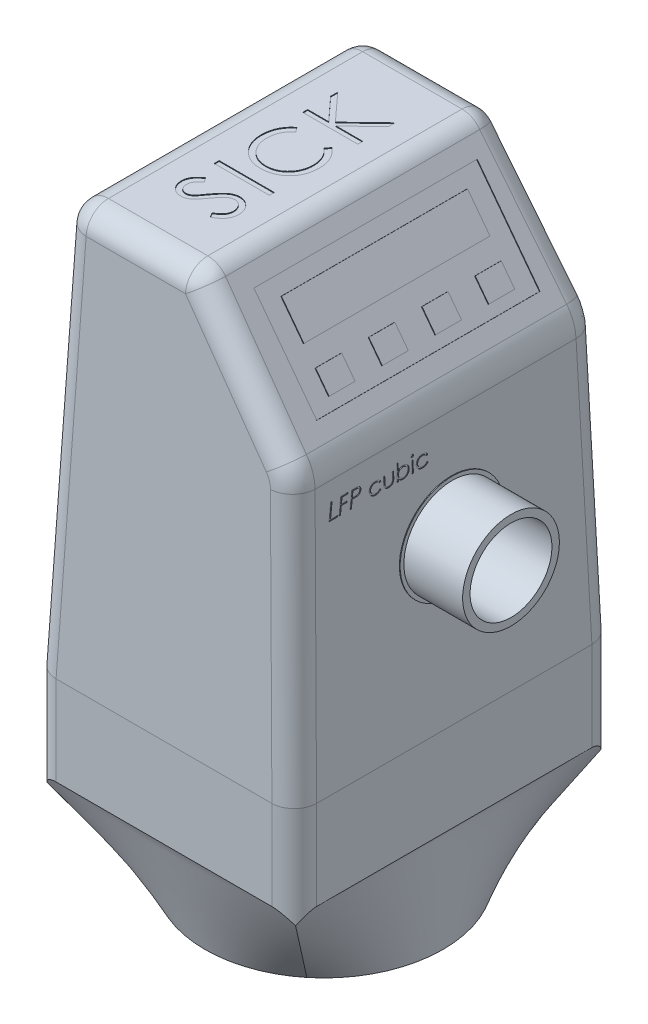
SolidWorks part; units mm, degrees
ref_plane "Ön Düzlem" through (0, 0, 0) normal (0, 0, 1) x (1, 0, 0)
ref_plane "Üst Düzlem" through (0, 0, 0) normal (0, 1, 0) x (1, 0, 0)
ref_plane "Sağ Düzlem" through (0, 0, 0) normal (1, 0, 0) x (0, 0, -1)
sketch "Sketch1" plane through (0, 0, 0) normal (0, 0, 1) x (1, 0, 0)
  line L0 (0, 0) -> (35, 0)
  line L1 (35, 0) -> (33.771, 37.3971)
  line L2 (33.771, 37.3971) -> (20.4579, 55)
  line L3 (20.4579, 55) -> (2.764, 55)
  line L4 (2.764, 55) -> (0, 0)
  dimension "D1" = 35
  dimension "D2" = 55
extrude "Boss-Extrude1" add sketch "Sketch1" along normal blind 43 contours L3 L4 L0 L1 L2 | L0 region at (16.9758, 25.3799, 0)
ref_plane "Plane1" through (0, 0, 0) normal (1, 0, 0) x (0, 0, -1)
sketch "Sketch9" plane through (0, 0, 0) normal (1, 0, 0) x (0, 0, -1)
  line L0 (0, 55) -> (-1.5, 55)
  line L1 (-43, 55) -> (0, 55) construction
  line L2 (-1.5, 55) -> (0, 0)
  line L3 (0, 0) -> (0, 55)
  line L4 (-43, 55) -> (-41.5, 55)
  line L5 (-41.5, 55) -> (-43, 0)
  line L6 (-43, 0) -> (-43, 55)
  dimension "D1" = 1.5
  dimension "D2" = 1.5
fillet "Fillet2" radius 6 1 edges at (33.771, 37.3971, 21.5)
extrude "Cut-Extrude5" cut sketch "Sketch9" along normal through all
fillet "Fillet3" radius 3 12 edges at (34.4168, 17.7469, 42.516) (33.4929, 37.2987, 41.9828) (26.5401, 46.958, 1.2807) (33.4929, 37.2987, 1.0172) (20.4579, 55, 21.5) (11.611, 55, 41.5) (2.764, 55, 21.5) (11.611, 55, 1.5) (26.5401, 46.958, 41.7193) (1.382, 27.5, 42.25) (1.382, 27.5, 0.75) (34.4168, 17.7469, 0.484)
sketch "Sketch10" plane through (0, 0, 0) normal (0, -1, 0) x (1, 0, 0)
  line L1 (0, 0) -> (35, 0)
  line L2 (0, 0) -> (0, 43)
  line L3 (0, 43) -> (35, 43)
  line L4 (35, 0) -> (35, 43)
  dimension "D1" = 35
  dimension "D2" = 43
extrude "Boss-Extrude2" add sketch "Sketch10" along normal blind 12
ref_plane "Plane4" through (0, -27, 0) normal (0, -1, 0) x (-1, 0, 0)
ref_plane "Plane5" through (0, -12, 0) normal (0, -1, 0) x (-1, 0, 0)
sketch "Sketch11" plane through (0, -12, 0) normal (0, -1, 0) x (-1, 0, 0)
  line L0 (-35, 0) -> (-35, -43) construction
  line L1 (-35, -43) -> (0, -43) construction
  line L2 (0, -43) -> (0, 0) construction
  line L3 (0, 0) -> (-35, 0) construction
  line L4 (-35, 0) -> (-35, -43)
  line L5 (-35, -43) -> (0, -43)
  line L6 (0, -43) -> (0, 0)
  line L7 (0, 0) -> (-35, 0)
sketch "Sketch12" plane through (0, -27, 0) normal (0, -1, 0) x (-1, 0, 0)
  circle A0 centre (-17.5, -21.5) radius 16
  dimension "D1" = 32
loft "Loft3" add profiles "Sketch12", "Sketch11" connector at (30.6019, -27, 12.3164) connector at (0, -12, 0)
fillet "Fillet4" radius 3 4 edges at (0, -6, 0) (0, -6, 43) (35, -6, 43) (35, -6, 0)
sketch "Sketch17" plane through (39.4751, 29.855, 0) normal (0.7976, 0.6032, 0) x (0, 0, -1)
  line L1 (-36.185, 27.7005) -> (-6.185, 27.7005)
  line L2 (-36.185, 27.7005) -> (-36.185, 13.7005)
  line L3 (-36.185, 13.7005) -> (-6.185, 13.7005)
  line L4 (-6.185, 27.7005) -> (-6.185, 13.7005)
  line L8 (-38.9869, 11.3605) -> (-4.0131, 11.3605) construction
  dimension "D1" = 30
  dimension "D2" = 14
  dimension "D3" = 2.34
extrude "Cut-Extrude6" cut sketch "Sketch17" against normal blind 0.1
sketch "Sketch18" plane through (39.3953, 29.7947, 0) normal (0.7976, 0.6032, 0) x (0, 0, -1)
  line L0 (-6.185, 27.7005) -> (-36.185, 27.7005) construction
  line L1 (-33.685, 25.7005) -> (-8.685, 25.7005)
  line L2 (-33.685, 25.7005) -> (-33.685, 20.7005)
  line L3 (-33.685, 20.7005) -> (-8.685, 20.7005)
  line L4 (-8.685, 25.7005) -> (-8.685, 20.7005)
  line L5 (-36.185, 27.7005) -> (-36.185, 13.7005) construction
  line L6 (-36.185, 27.7005) -> (-36.185, 13.7005) construction
  line L7 (-33.685, 18.1005) -> (-30.185, 18.1005)
  line L8 (-33.685, 18.1005) -> (-33.685, 15.1005)
  line L9 (-33.685, 15.1005) -> (-30.185, 15.1005)
  line L10 (-30.185, 18.1005) -> (-30.185, 15.1005)
  line L11 (-36.185, 13.7005) -> (-6.185, 13.7005) construction
  line L12 (-26.535, 18.1005) -> (-23.035, 18.1005)
  line L13 (-23.035, 18.1005) -> (-23.035, 15.1005)
  line L14 (-26.535, 15.1005) -> (-23.035, 15.1005)
  line L15 (-26.535, 18.1005) -> (-26.535, 15.1005)
  line L16 (-19.385, 18.1005) -> (-15.885, 18.1005)
  line L17 (-15.885, 18.1005) -> (-15.885, 15.1005)
  line L18 (-19.385, 15.1005) -> (-15.885, 15.1005)
  line L19 (-19.385, 18.1005) -> (-19.385, 15.1005)
  line L20 (-12.235, 18.1005) -> (-8.735, 18.1005)
  line L21 (-8.735, 18.1005) -> (-8.735, 15.1005)
  line L22 (-12.235, 15.1005) -> (-8.735, 15.1005)
  line L23 (-12.235, 18.1005) -> (-12.235, 15.1005)
  dimension "D1" = 25
  dimension "D2" = 2
  dimension "D3" = 5
  dimension "D4" = 2.5
  dimension "D5" = 3
  dimension "D6" = 3.5
  dimension "D7" = 2.5
  dimension "D8" = 1.4
  dimension "D9" = 4
extrude "Boss-Extrude3" add sketch "Sketch18" along normal blind 0.1
ref_plane "Plane6" through (23.9722, 50.3533, 33.685) normal (0, 0, 1) x (1, 0, 0)
sketch "Sketch23" plane through (0, 55, 0) normal (0, 1, 0) x (1, 0, 0)
  line L0 (16.0636, -35.984) -> (16.0636, -8.2235) construction
  text T0 "SICK" font "Century Gothic" height in points 28
extrude "Cut-Extrude8" cut sketch "Sketch23" against normal blind 0.1
sketch "Sketch24" plane through (34.9622, 1.149, 0) normal (0.9995, 0.0328, 0) x (0, 0, -1)
  line L0 (-37.3722, 29.7813) -> (-9.3394, 29.7813) construction
  text T0 "<i>LFP</i> cubic" font "Century Gothic" height in points 8
extrude "Cut-Extrude9" cut sketch "Sketch24" against normal blind 0.1
ref_plane "Plane7" through (35, 0, 0) normal (1, 0, 0) x (0, 0, -1)
sketch "Sketch25" plane through (35, 0, 0) normal (1, 0, 0) x (0, 0, -1)
  circle A0 centre (-21.8692, 22.0718) radius 6.5
  circle A1 centre (-21.8692, 22.0718) radius 5.5
  dimension "D1" = 13
  dimension "D2" = 11
extrude "Boss-Extrude4" add sketch "Sketch25" along normal blind 8 separate body
sketch "Sketch26" plane through (35, 0, 0) normal (1, 0, 0) x (0, 0, -1)
  circle A0 centre (-21.8692, 22.0718) radius 7
  dimension "D1" = 14
extrude "Boss-Extrude5" add sketch "Sketch26" along normal blind 0.1
equation "\"D4@Sketch18\"=(\"D1@Sketch17\"-\"D1@Sketch18\")/2"
